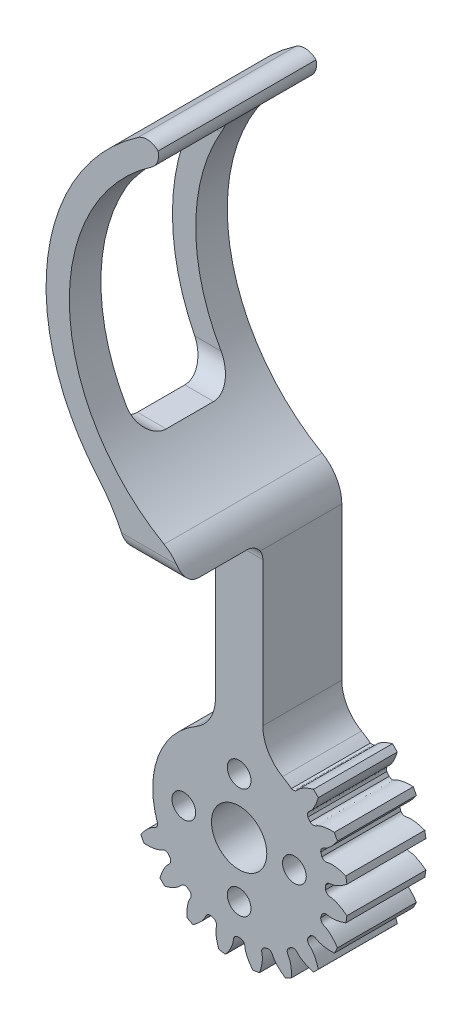
SolidWorks part; units mm, degrees
material "聚脂树脂"
ref_plane "前视基准面" through (0, 0, 0) normal (0, 0, 1) x (1, 0, 0)
ref_plane "上视基准面" through (0, 0, 0) normal (0, 1, 0) x (1, 0, 0)
ref_plane "右视基准面" through (0, 0, 0) normal (1, 0, 0) x (0, 0, -1)
other "Configuration Table"
sketch "草图1" plane through (0, 0, 0) normal (0, 0, 1) x (1, 0, 0)
  circle A0 centre (0, 0) radius 13.75
extrude "凸台-拉伸1" add sketch "草图1" along normal blind 10
ref_axis "基准轴1" through (0, 0, -1.5) along (0, 0, 1)
sketch "草图2" plane through (0, 0, 0) normal (0, 0, 1) x (1, 0, 0)
  line L0 (0, 0) -> (0, 13.75) construction
  circle A0 centre (0, 0) radius 13.75 construction
  arc A1 (0.2416, 10.9348) -> (-0.2416, 10.9348) centre (0, 0) ccw
  arc A2 (3.9764, 15.6228) -> (-3.9764, 15.6228) centre (0, 0) ccw
  spline S0 degree 3 poles (0.2416, 10.9348) (0.764, 11.1168) (0.6964, 11.4839) (0.7661, 11.8375) (0.7736, 11.8719) (0.7829, 11.9108) (0.7941, 11.954) (0.8075, 12.0015) (0.8231, 12.0532) (0.8413, 12.1091) (0.8621, 12.169) (0.8857, 12.2329) (0.9123, 12.3007) (0.9421, 12.3723) (0.9752, 12.4476) (1.0117, 12.5264) (1.0519, 12.6088) (1.0959, 12.6945) (1.1438, 12.7834) (1.1957, 12.8755) (1.2519, 12.9705) (1.3125, 13.0684) (1.3775, 13.1691) (1.4472, 13.2723) (1.5216, 13.3779) (1.601, 13.4858) (1.6853, 13.5958) (1.7747, 13.7078) (1.8694, 13.8216) (1.9693, 13.937) (2.0748, 14.0539) (2.1857, 14.1721) (2.3023, 14.2914) (2.4246, 14.4116) (2.5527, 14.5326) (2.6866, 14.6542) (2.8265, 14.7761) (2.9725, 14.8983) (3.1245, 15.0204) (3.2826, 15.1424) (3.4469, 15.2639) (3.6768, 15.427) (3.8549, 15.5454) (3.9764, 15.6228) knots 0 0 0 0 0.165916 0.170906 0.176664 0.183189 0.190482 0.198542 0.207371 0.216967 0.22733 0.238462 0.250361 0.263027 0.276462 0.290664 0.305634 0.321371 0.337876 0.355149 0.37319 0.391998 0.411574 0.431917 0.453028 0.474907 0.497554 0.520968 0.54515 0.570099 0.595817 0.622302 0.649554 0.677575 0.706363 0.735918 0.766242 0.797333 0.829191 0.861818 0.895212 0.929373 1 1 1 1
  spline S1 degree 3 poles (-0.2416, 10.9348) (-0.764, 11.1168) (-0.6964, 11.4839) (-0.7661, 11.8375) (-0.7736, 11.8719) (-0.7829, 11.9108) (-0.7941, 11.954) (-0.8075, 12.0015) (-0.8231, 12.0532) (-0.8413, 12.1091) (-0.8621, 12.169) (-0.8857, 12.2329) (-0.9123, 12.3007) (-0.9421, 12.3723) (-0.9752, 12.4476) (-1.0117, 12.5264) (-1.0519, 12.6088) (-1.0959, 12.6945) (-1.1438, 12.7834) (-1.1957, 12.8755) (-1.2519, 12.9705) (-1.3125, 13.0684) (-1.3775, 13.1691) (-1.4472, 13.2723) (-1.5216, 13.3779) (-1.601, 13.4858) (-1.6853, 13.5958) (-1.7747, 13.7078) (-1.8694, 13.8216) (-1.9693, 13.937) (-2.0748, 14.0539) (-2.1857, 14.1721) (-2.3023, 14.2914) (-2.4246, 14.4116) (-2.5527, 14.5326) (-2.6866, 14.6542) (-2.8265, 14.7761) (-2.9725, 14.8983) (-3.1245, 15.0204) (-3.2826, 15.1424) (-3.4469, 15.2639) (-3.6768, 15.427) (-3.8549, 15.5454) (-3.9764, 15.6228) knots 0 0 0 0 0.165916 0.170906 0.176664 0.183189 0.190482 0.198542 0.207371 0.216967 0.22733 0.238462 0.250361 0.263027 0.276462 0.290664 0.305634 0.321371 0.337876 0.355149 0.37319 0.391998 0.411574 0.431917 0.453028 0.474907 0.497554 0.520968 0.54515 0.570099 0.595817 0.622302 0.649554 0.677575 0.706363 0.735918 0.766242 0.797333 0.829191 0.861818 0.895212 0.929373 1 1 1 1
extrude "切除-拉伸1" cut sketch "草图2" along normal through all
pattern_circular "阵列(圆周)1" count 20 every 18 about axis through (0, 0, -1.5) along (0, 0, 1) of "切除-拉伸1"
sketch "草图6" plane through (0, 0, 0) normal (0, 0, -1) x (-1, 0, 0)
  line L0 (0, 0) -> (0, 65.9124) construction
  line L1 (0, 0) -> (39.45, 0) construction
  line L2 (0, 0) -> (-30.8379, 0) construction
  line L3 (-12.5, 0) -> (-12.5, 56.4778) construction
  line L4 (3, 0) -> (3, 36.1803)
  line L5 (-3, 0) -> (-3, 36.1803)
  line L6 (-3, 36.1803) -> (-3, 74.6745)
  line L7 (-3, 74.6745) -> (-12.5, 58.22) construction
  line L8 (-3, 74.6745) -> (6.3052, 90.7916) construction
  line L9 (-3, 74.6745) -> (0.9722, 81.5545)
  line L10 (-3, 0) -> (3, 0)
  line L11 (-5.8534, 12.4419) -> (-3, 14.0893)
  line L12 (5.8534, 12.4419) -> (3, 14.0893)
  circle A0 centre (0, 0) radius 12.5 construction
  circle A1 centre (-12.5, 58.22) radius 24 construction
  circle A2 centre (-12.5, 58.22) radius 26.9444 construction
  arc A3 (0.9722, 81.5545) -> (3, 36.1803) centre (-12.5, 58.22) cw
  arc A4 (-0.5, 79.0046) -> (-3, 36.1803) centre (-12.5, 58.22) cw
  spline S0 degree 3 poles (4170.5193, 2761.6364) (-39.5872, -22.7775) (-1.2316, 5.367) (-4.3931, 11.033) (-4.4189, 11.076) (-4.4589, 11.1387) (-4.5098, 11.2131) (-4.5827, 11.3111) (-4.6712, 11.4208) (-4.7765, 11.541) (-4.8994, 11.6706) (-5.0408, 11.8083) (-5.2016, 11.9528) (-5.3825, 12.1027) (-5.5474, 12.2287) (-5.6899, 12.331) (-32.2815, 30.6309) (-182.3451, -134.4638) (4620.1527, 1908.3045) knots -2.997011 -2.997011 -2.997011 -2.997011 0.165916 0.170906 0.183189 0.190482 0.207371 0.22733 0.250361 0.276462 0.305634 0.337876 0.37319 0.411574 0.453028 0.474907 0.497554 16.274884 16.274884 16.274884 16.274884 only from (-3.6089, 10.325) to (-5.8534, 12.4419) construction
  spline S1 degree 3 poles (-3, 10.4088) (-4.144, 10.1273) (-4.1641, 10.6226) (-4.3931, 11.033) (-4.4189, 11.076) (-4.4589, 11.1387) (-4.5098, 11.2131) (-4.5827, 11.3111) (-4.6712, 11.4208) (-4.7765, 11.541) (-4.8994, 11.6706) (-5.0408, 11.8083) (-5.2016, 11.9528) (-5.3825, 12.1027) (-5.5842, 12.2567) (-5.7442, 12.3691) (-5.8366, 12.4308) (-5.8534, 12.4419) knots -0.047197 -0.047197 -0.047197 -0.047197 0.165916 0.170906 0.183189 0.190482 0.207371 0.22733 0.250361 0.276462 0.305634 0.337876 0.37319 0.411574 0.453028 0.497554 0.507432 0.507432 0.507432 0.507432
  spline S2 degree 3 poles (-4170.5193, 2761.6364) (39.5872, -22.7775) (1.2316, 5.367) (4.3931, 11.033) (4.4189, 11.076) (4.4589, 11.1387) (4.5098, 11.2131) (4.5827, 11.3111) (4.6712, 11.4208) (4.7765, 11.541) (4.8994, 11.6706) (5.0408, 11.8083) (5.2016, 11.9528) (5.3825, 12.1027) (5.5474, 12.2287) (5.6899, 12.331) (32.2815, 30.6309) (182.3451, -134.4638) (-4620.1527, 1908.3045) knots -2.504443 -2.504443 -2.504443 -2.504443 0.658484 0.663474 0.675757 0.68305 0.699939 0.719899 0.742929 0.76903 0.798202 0.830445 0.865758 0.904142 0.945597 0.967475 0.990122 16.767452 16.767452 16.767452 16.767452 only from (3.6089, 10.325) to (5.8534, 12.4419) construction
  spline S3 degree 3 poles (3, 10.4088) (4.144, 10.1273) (4.1641, 10.6226) (4.3931, 11.033) (4.4189, 11.076) (4.4589, 11.1387) (4.5098, 11.2131) (4.5827, 11.3111) (4.6712, 11.4208) (4.7765, 11.541) (4.8994, 11.6706) (5.0408, 11.8083) (5.2016, 11.9528) (5.3825, 12.1027) (5.5842, 12.2567) (5.7442, 12.3691) (5.8366, 12.4308) (5.8534, 12.4419) knots 0.445372 0.445372 0.445372 0.445372 0.658484 0.663474 0.675757 0.68305 0.699939 0.719899 0.742929 0.76903 0.798202 0.830445 0.865758 0.904142 0.945597 0.990122 1 1 1 1
  dimension "D1" = 25
  dimension "D4" = 48
  dimension "D5" = 30
  dimension "D2" = 6
  dimension "D3" = 58.22
  dimension "D6" = 60
  dimension "D7" = 60
extrude "凸台-拉伸2" add sketch "草图6" against normal blind 20 contours A3 L9 L6 L5 L10 L4 | S1 L5 L11 | L4 S3 L12 region at (0, 0.834, 0) region at (-3.9534, 12.128, 0) region at (3.9534, 12.128, 0)
sketch "草图7" plane through (3, 0, 0) normal (1, 0, 0) x (0, 0, -1)
  line L2 (-20, 14.0893) -> (-20, 36.1803) construction
  line L7 (-5, 2.5777) -> (-5, 27.3083) construction
  line L8 (-10, 2.5777) -> (0, 2.5777) construction
  line L9 (-20, 34) -> (-20, 0)
  line L10 (-10, 34) -> (-20, 34)
  line L11 (-10, 0) -> (-10, 34)
  line L12 (-20, 0) -> (-10, 0)
  line L13 (-10, 10.4088) -> (-10, 0) construction
  dimension "D1" = 34
  dimension "D2" = 10
extrude "切除-拉伸3" cut sketch "草图7" against normal blind 32 and the other way blind 10
ref_plane "基准面1" through (12.5, 0, 0) normal (1, 0, 0) x (0, 0, -1)
fillet "圆角2" radius 2 2 edges at (0, 34, 10) (0, 34, 20)
sketch "草图4" plane through (0, 0, 10) normal (0, 0, 1) x (1, 0, 0)
  line L0 (0, 0) -> (0, 14.4175) construction
  line L1 (0, 0) -> (19.7904, 0) construction
  circle A0 centre (0, 0) radius 9
  circle A1 centre (0, 0) radius 3.5
  circle A2 centre (0, 7) radius 1.5
  circle A3 centre (7, 0) radius 1.5
  circle A4 centre (0, -7) radius 1.5
  circle A5 centre (-7, 0) radius 1.5
  dimension "D1" = 18
  dimension "D2" = 7
  dimension "D3" = 3
  dimension "D4" = 3
  dimension "D5" = 7
  dimension "D6" = 7
extrude "切除-拉伸2" cut sketch "草图4" against normal blind 20 contours A1 | A5 | A2 | A3 | A4
ref_plane "基准面2" through (0, 0, 9) normal (0, 0, 1) x (1, 0, 0)
sketch "草图17" plane through (0, 0, 10) normal (0, 0, 1) x (1, 0, 0)
  line L0 (0, 0) -> (-6.6228, 8.7044)
  line L1 (-6.6228, 8.7044) -> (-11.857, 15.5837)
  line L2 (0, 0) -> (-10.325, -3.6089)
  line L3 (-10.325, -3.6089) -> (-17.9409, -6.2709)
  circle A0 centre (0, 0) radius 10.9375
  arc A1 (-6.2318, 8.9885) -> (-6.6228, 8.7044) centre (0, 0) ccw construction
  circle A2 centre (0, 0) radius 17.5
  dimension "D1" = 35
extrude "切除-拉伸5" cut sketch "草图17" against normal blind 10 contours L1 A2 L3 A0 region at (-12.9643, 3.8979, 10)
fillet "圆角3" radius 20 1 edges at (-3, 36.1803, 10)
fillet "圆角4" radius 5 1 edges at (3, 36.1803, 10)
fillet "圆角5" radius 2 2 edges at (-0.9722, 81.5545, 10) (0.5, 79.0046, 10)
sketch "草图19" plane through (12.5, 0, 0) normal (1, 0, 0) x (0, 0, -1)
  line L0 (-5, 0.2416) -> (-5, 85.5937) construction
  line L1 (-10, 0.2416) -> (0, 0.2416) construction
  line L2 (0, 37.4354) -> (0, 78.0199) construction
  line L5 (-16, 43.22) -> (-4, 43.22)
  line L6 (-16, 43.22) -> (-16, 73.22)
  line L7 (-16, 73.22) -> (-4, 73.22)
  line L8 (-4, 43.22) -> (-4, 73.22)
  line L9 (-16, 43.22) -> (-4, 73.22) construction
  line L10 (-16, 73.22) -> (-4, 43.22) construction
  point P4 (-10, 58.22)
  dimension "D3" = 4
  dimension "D1" = 30
  dimension "D2" = 58.22
  dimension "D4" = 12
extrude "切除-拉伸6" cut sketch "草图19" against normal blind 55
fillet "圆角6" radius 3 4 edges at (-8.059, 43.22, 4) (-8.059, 43.22, 16) (-8.059, 73.22, 16) (-8.059, 73.22, 4)
sketch "草图20" plane through (0, 0, 0) normal (0, 0, -1) x (-1, 0, 0)
  line L0 (-3, 14.0893) -> (-3, 10.518)
  line L1 (3, 14.0893) -> (3, 10.518)
  line L2 (5.8534, 12.4419) -> (3, 14.0893) construction
  line L3 (-5.8534, 12.4419) -> (-3, 14.0893) construction
  line L4 (5.8534, 12.4419) -> (3, 14.0893)
  line L5 (-5.8534, 12.4419) -> (-3, 14.0893)
  circle A0 centre (0, 0) radius 10.9375
  arc A1 (10.325, -3.6089) -> (6.2318, 8.9885) centre (0, 0) ccw construction
  arc A2 (6.6252, 12.0486) -> (5.8534, 12.4419) centre (0, 0) ccw construction
  arc A3 (-5.8534, 12.4419) -> (-6.6252, 12.0486) centre (0, 0) ccw construction
  arc A4 (6.6252, 12.0486) -> (5.8534, 12.4419) centre (0, 0) ccw
  arc A5 (-5.8534, 12.4419) -> (-6.6252, 12.0486) centre (0, 0) ccw
  spline S0 degree 3 poles (1876.625, -698.848) (-20.9969, 12.4766) (4.3246, 5.6774) (6.3437, 10.0391) (6.3633, 10.0853) (6.3905, 10.1545) (6.4208, 10.2394) (6.4573, 10.356) (6.4939, 10.4921) (6.5293, 10.6479) (6.5619, 10.8235) (6.5902, 11.0188) (6.6126, 11.2338) (6.6276, 11.4683) (6.6325, 11.6758) (6.6315, 11.8512) (6.0134, 36.0214) (-118.4428, 55.7409) (1694.3797, -1060.7669) knots -2.172632 -2.172632 -2.172632 -2.172632 0.165916 0.170906 0.183189 0.190482 0.207371 0.22733 0.250361 0.276462 0.305634 0.337876 0.37319 0.411574 0.453028 0.474907 0.497554 12.30377 12.30377 12.30377 12.30377 only from (6.2318, 8.9885) to (6.6252, 12.0486) construction
  spline S1 degree 3 poles (-1876.625, -698.848) (20.9969, 12.4766) (-4.3246, 5.6774) (-6.3437, 10.0391) (-6.3633, 10.0853) (-6.3905, 10.1545) (-6.4208, 10.2394) (-6.4573, 10.356) (-6.4939, 10.4921) (-6.5293, 10.6479) (-6.5619, 10.8235) (-6.5902, 11.0188) (-6.6126, 11.2338) (-6.6276, 11.4683) (-6.6325, 11.6758) (-6.6315, 11.8512) (-6.0134, 36.0214) (118.4428, 55.7409) (-1694.3797, -1060.7669) knots -1.680063 -1.680063 -1.680063 -1.680063 0.658484 0.663474 0.675757 0.68305 0.699939 0.719899 0.742929 0.76903 0.798202 0.830445 0.865758 0.904142 0.945597 0.967475 0.990122 12.796339 12.796339 12.796339 12.796339 only from (-6.2318, 8.9885) to (-6.6252, 12.0486) construction
  spline S2 degree 3 poles (6.2318, 8.9885) (5.9162, 9.4428) (6.1867, 9.7) (6.3437, 10.0391) (6.3633, 10.0853) (6.3905, 10.1545) (6.4208, 10.2394) (6.4573, 10.356) (6.4939, 10.4921) (6.5293, 10.6479) (6.5619, 10.8235) (6.5902, 11.0188) (6.6126, 11.2338) (6.6276, 11.4683) (6.6336, 11.722) (6.6305, 11.9176) (6.6261, 12.0285) (6.6252, 12.0486) knots 0 0 0 0 0.165916 0.170906 0.183189 0.190482 0.207371 0.22733 0.250361 0.276462 0.305634 0.337876 0.37319 0.411574 0.453028 0.497554 0.507432 0.507432 0.507432 0.507432
  spline S3 degree 3 poles (-6.2318, 8.9885) (-5.9162, 9.4428) (-6.1867, 9.7) (-6.3437, 10.0391) (-6.3633, 10.0853) (-6.3905, 10.1545) (-6.4208, 10.2394) (-6.4573, 10.356) (-6.4939, 10.4921) (-6.5293, 10.6479) (-6.5619, 10.8235) (-6.5902, 11.0188) (-6.6126, 11.2338) (-6.6276, 11.4683) (-6.6336, 11.722) (-6.6305, 11.9176) (-6.6261, 12.0285) (-6.6252, 12.0486) knots 0.492568 0.492568 0.492568 0.492568 0.658484 0.663474 0.675757 0.68305 0.699939 0.719899 0.742929 0.76903 0.798202 0.830445 0.865758 0.904142 0.945597 0.990122 1 1 1 1
extrude "切除-拉伸7" cut sketch "草图20" against normal blind 10 contours S3 A0 L0 L5 A5 | A0 S2 A4 L4 L1 region at (4.6909, 11.5198, 0) region at (-4.6909, 11.5198, 0)
fillet "圆角7" radius 5 2 edges at (-3, 10.518, 5) (3, 10.518, 5)
